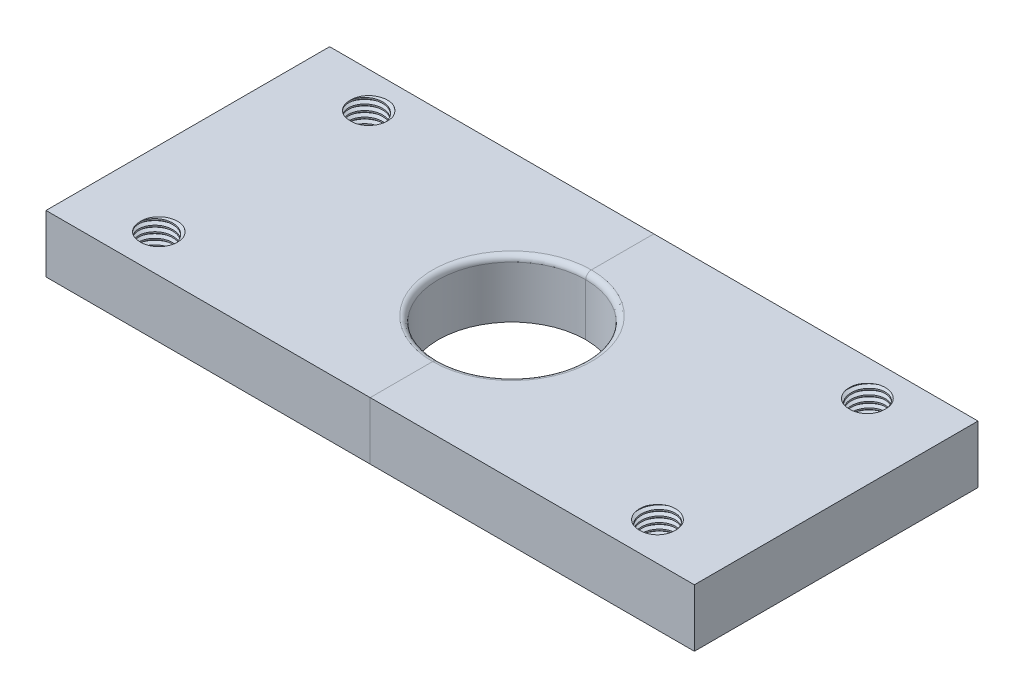
SolidWorks part; units mm, degrees
material "Aleación 6061"
ref_plane "Alzado" through (0, 0, 0) normal (0, 0, 1) x (1, 0, 0)
ref_plane "Planta" through (0, 0, 0) normal (0, 1, 0) x (1, 0, 0)
ref_plane "Vista lateral" through (0, 0, 0) normal (1, 0, 0) x (0, 0, -1)
sketch "Croquis2" plane through (0, 0, 0) normal (0, 1, 0) x (1, 0, 0)
  line L0 (0, 25) -> (-57.15, 25)
  line L4 (-57.15, 25) -> (-57.15, -25)
  line L8 (0, -25) -> (0, -13)
  line L9 (0, 13) -> (0, 25)
  line L11 (0, -25) -> (-57.15, -25)
  line L12 (0, 32.9631) -> (0, -34.8375) construction
  circle A0 centre (-44.15, -18.5) radius 3
  arc A2 (0, 13) -> (0, -13) centre (0, 0) ccw
  circle A5 centre (-44.15, 18.5) radius 3
  point P0 (0, 0)
  dimension "D3" = 25
  dimension "D4" = 13
  dimension "D6" = 6
  dimension "D7" = 6
  dimension "D9" = 13
  dimension "D1" = 50
  dimension "D2" = 57.15
extrude "Saliente-Extruir1" add sketch "Croquis2" along normal blind 10.16
fillet "Redondeo5" radius 1 1 edges at (-13, 10.16, 0)
ref_plane "Plano5" through (0, 0, 0) normal (1, 0, 0) x (0, 0, -1)
thread "Rosca3" pitch 1 start angle 0, offset 0, length 20, pitch 1, diameter 6
ref_plane "Plano3" through (-47.15, 10.91, -18.5) normal (0, 0, 1) x (-1, 0, 0)
sketch "Perfil de rosca3" plane through (-47.15, 10.91, -18.5) normal (0, 0, 1) x (-1, 0, 0)
  line L0 (0, 0) -> (0, 1) construction
  line L1 (0, 0) -> (0.5413, 0.3125)
  line L2 (0.5413, 0.3125) -> (0.5413, 0.4375)
  line L3 (0.5413, 0.4375) -> (0, 0.75)
  line L4 (0.5413, 0.375) -> (0, 0.375) construction
  line L11 (0, 0) -> (0, 0.75)
  point P2 (0, 0)
  dimension "Pitch" = 1
  dimension "Profile_Angle" = 60
  dimension "Profile_Land" = 0.125
  dimension "Profile_Height" = 0.5413
thread "Rosca1" pitch 1 profile "Perfil de rosca1" start angle 0, offset 0, length 0, pitch 1, diameter 6
ref_plane "Plano1" through (-47.15, 10.91, 18.5) normal (0, 0, 1) x (-1, 0, 0)
sketch "Perfil de rosca1" plane through (-47.15, 10.91, 18.5) normal (0, 0, 1) x (-1, 0, 0)
  line L0 (0, 0) -> (0, 1) construction
  line L1 (0, 0) -> (0.5413, 0.3125)
  line L2 (0.5413, 0.3125) -> (0.5413, 0.4375)
  line L3 (0.5413, 0.4375) -> (0, 0.75)
  line L4 (0.5413, 0.375) -> (0, 0.375) construction
  line L11 (0, 0) -> (0, 0.75)
  point P2 (0, 0)
  dimension "Pitch" = 1
  dimension "Profile_Angle" = 60
  dimension "Profile_Land" = 0.125
  dimension "Profile_Height" = 0.5413
mirror "Simetría2" about plane through (0, 0, 0) normal (1, 0, 0) of bodies 102 105
